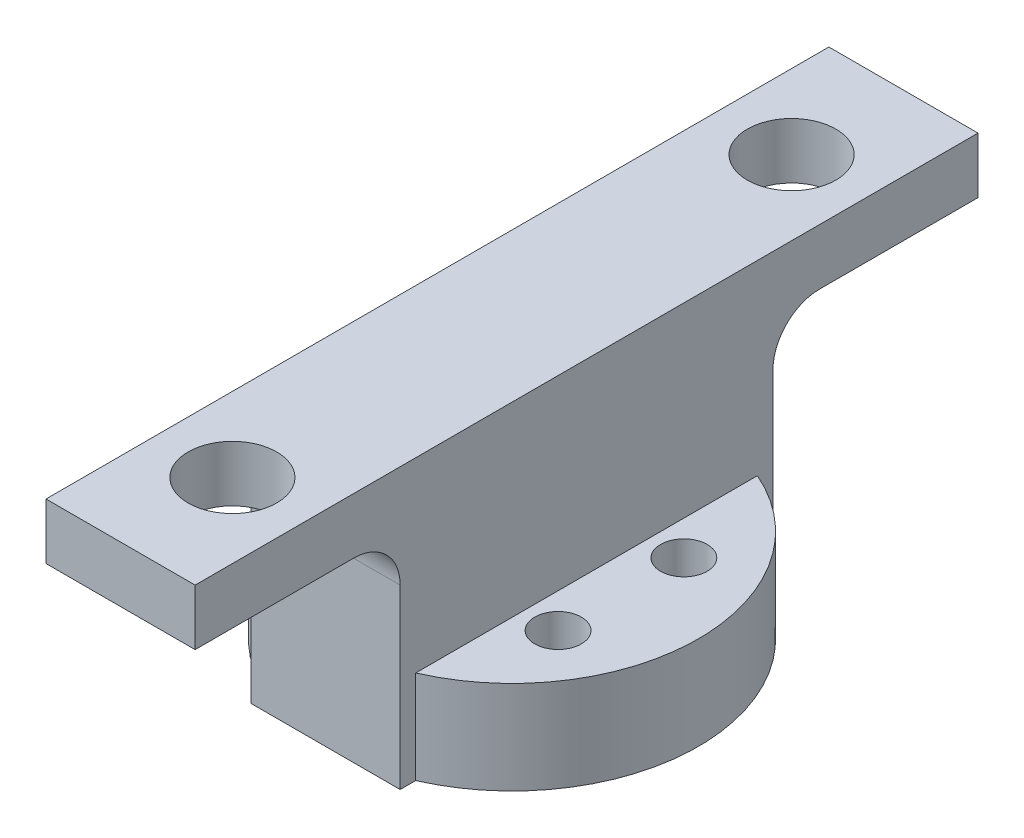
SolidWorks part; units mm, degrees
ref_plane "Front Plane" through (0, 0, 0) normal (0, 0, 1) x (1, 0, 0)
ref_plane "Top Plane" through (0, 0, 0) normal (0, 1, 0) x (1, 0, 0)
ref_plane "Right Plane" through (0, 0, 0) normal (1, 0, 0) x (0, 0, -1)
sketch "Sketch1" plane through (0, 0, 0) normal (0, 1, 0) x (1, 0, 0)
  arc A0 (14.1913, -6.75) -> (9.1913, -6.75) centre (11.6913, -6.75) ccw
  arc A1 (9.1913, -6.75) -> (14.1913, -6.75) centre (11.6913, -6.75) ccw
  arc A2 (2.5, -13.5) -> (-2.5, -13.5) centre (0, -13.5) ccw
  arc A3 (-2.5, -13.5) -> (2.5, -13.5) centre (0, -13.5) ccw
  arc A4 (-9.1913, -6.75) -> (-14.1913, -6.75) centre (-11.6913, -6.75) ccw
  arc A5 (-14.1913, -6.75) -> (-9.1913, -6.75) centre (-11.6913, -6.75) ccw
  arc A6 (-9.1913, 6.75) -> (-14.1913, 6.75) centre (-11.6913, 6.75) ccw
  arc A7 (-14.1913, 6.75) -> (-9.1913, 6.75) centre (-11.6913, 6.75) ccw
  arc A8 (-5.5, 0) -> (5.5, 0) centre (0, 0) ccw
  arc A9 (5.5, 0) -> (-5.5, 0) centre (0, 0) ccw
  arc A10 (2.5, 13.5) -> (-2.5, 13.5) centre (0, 13.5) ccw
  arc A11 (-2.5, 13.5) -> (2.5, 13.5) centre (0, 13.5) ccw
  arc A12 (14.1913, 6.75) -> (9.1913, 6.75) centre (11.6913, 6.75) ccw
  arc A13 (9.1913, 6.75) -> (14.1913, 6.75) centre (11.6913, 6.75) ccw
  circle A14 centre (0, 0) radius 20
extrude "Boss-Extrude1" add sketch "Sketch1" along normal blind 10 contours A8 A9 | A14 A1 A0 A3 A2 A5 A4 A7 A6 A9 A8 A11 A10 A13 A12 region at (0, 0, 0) region at (-19.4343, 0, 0)
sketch "Sketch2" plane through (0, 10, 0) normal (0, 1, 0) x (1, 0, 0)
  line L1 (-8, -20) -> (8, -20)
  line L2 (-8, -20) -> (-8, 20)
  line L3 (-8, 20) -> (8, 20)
  line L4 (8, -20) -> (8, 20)
  line L5 (-8, -20) -> (8, 20) construction
  line L6 (-8, 20) -> (8, -20) construction
  point P0 (0, 0)
  dimension "D1" = 16
extrude "Boss-Extrude2" add sketch "Sketch2" along normal blind 20
sketch "Sketch3" plane through (0, 30, 0) normal (0, 1, 0) x (1, 0, 0)
  line L0 (0, 0) -> (0, 30) construction
  line L1 (0, 0) -> (0, -30) construction
  line L3 (-8, -20) -> (8, -20)
  line L4 (-8, -20) -> (-8, -42)
  line L5 (-8, -42) -> (8, -42)
  line L6 (8, -20) -> (8, -42)
  line L7 (-8, 20) -> (8, 20)
  line L8 (-8, 20) -> (-8, 42)
  line L9 (-8, 42) -> (8, 42)
  line L10 (8, 20) -> (8, 42)
  circle A0 centre (0, 30) radius 4.75
  circle A1 centre (0, -30) radius 4.75
  dimension "D2" = 9.5
  dimension "D1" = 30
  dimension "D3" = 22
extrude "Boss-Extrude3" add sketch "Sketch3" against normal blind 6
fillet "Fillet1" radius 5 2 edges at (0, 24, -20) (0, 24, 20)
sketch "Sketch4" plane through (0, 10, 0) normal (0, -1, 0) x (1, 0, 0)
  line L0 (-8, -20) -> (0, -20) construction
  line L1 (-8, -18.3303) -> (-8, -20) construction
  line L2 (8, -20) -> (8, -18.3303) construction
  line L3 (0, -20) -> (8, -20) construction
  line L4 (8, 20) -> (0, 20) construction
  line L5 (8, 18.3303) -> (8, 20) construction
  line L6 (-8, 20) -> (-8, 18.3303) construction
  line L7 (0, 20) -> (-8, 20) construction
  line L8 (-8, -20) -> (0, -20)
  line L9 (-8, -18.3303) -> (-8, -20)
  line L10 (8, -20) -> (8, -18.3303)
  line L11 (0, -20) -> (8, -20)
  line L12 (8, 20) -> (0, 20)
  line L13 (8, 18.3303) -> (8, 20)
  line L14 (-8, 20) -> (-8, 18.3303)
  line L15 (0, 20) -> (-8, 20)
  arc A0 (-8, -18.3303) -> (0, -20) centre (0, 0) ccw construction
  arc A1 (0, -20) -> (8, -18.3303) centre (0, 0) ccw construction
  arc A2 (8, 18.3303) -> (0, 20) centre (0, 0) ccw construction
  arc A3 (0, 20) -> (-8, 18.3303) centre (0, 0) ccw construction
  arc A4 (-8, -18.3303) -> (0, -20) centre (0, 0) ccw
  arc A5 (0, -20) -> (8, -18.3303) centre (0, 0) ccw
  arc A6 (8, 18.3303) -> (0, 20) centre (0, 0) ccw
  arc A7 (0, 20) -> (-8, 18.3303) centre (0, 0) ccw
  line M1 (-8, 20) -> (-8, 18.3303)
  arc M2 (-8, 18.3303) -> (0, 20) centre (0, 0) cw
  line M3 (0, 20) -> (-8, 20)
extrude "Boss-Extrude4" add sketch "Sketch4" along normal up to surface (10 mm away) contours M3 M1 M2 | A6 L13 L12 | A5 L11 L10 | A4 L9 L8 region at (-6.0171, 10, -19.5029) region at (6.0171, 10, -19.5029) region at (6.0171, 10, 19.5029) region at (-6.0171, 10, 19.5029) up to face at (11.6913, 0, 9.25)
